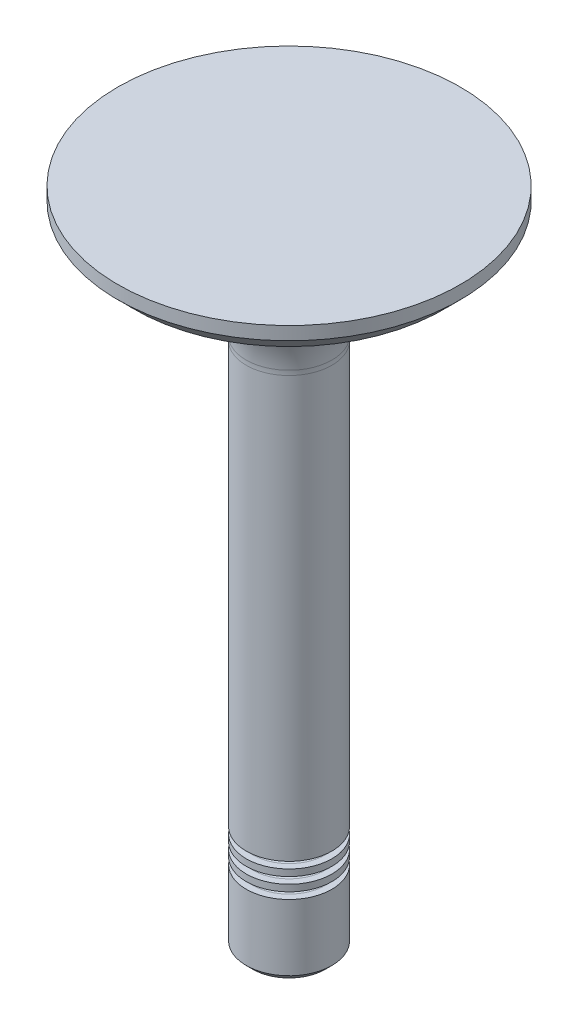
SolidWorks part; units mm, degrees
ref_plane "Front Plane" through (0, 0, 0) normal (0, 0, 1) x (1, 0, 0)
ref_plane "Top Plane" through (0, 0, 0) normal (0, 1, 0) x (1, 0, 0)
ref_plane "Right Plane" through (0, 0, 0) normal (1, 0, 0) x (0, 0, -1)
sketch "Sketch1" plane through (0, 0, 0) normal (0, 0, 1) x (1, 0, 0)
  line L0 (0, 224.083) -> (0, 124.083) construction
  line L1 (0, 224.083) -> (-25.92, 224.083)
  line L2 (-25.92, 224.083) -> (-25.92, 222.083)
  line L3 (-25.92, 222.083) -> (-23.328, 219.491)
  line L5 (-6.48, 204.053) -> (-6.48, 124.083)
  line L6 (-6.48, 124.083) -> (0, 124.083)
  line L7 (0, 224.083) -> (0, 124.083)
  arc A3 (-23.328, 219.491) -> (-6.48, 204.053) centre (-22.623, 203.348) cw
  dimension "D1" = 25.92
  dimension "D2" = 45
  dimension "D4" = 6.48
  dimension "D5" = 18.03
  dimension "D7" = 100
  dimension "D3" = 2.592
  dimension "D6" = 2
revolve "Revolve1" add sketch "Sketch1" angle 360 about L0
fillet "Fillet1" radius 10 1 edges at (-6.48, 204.053, 0)
chamfer "Chamfer1" distance 1 angle 45 1 edges at (-6.48, 124.083, 0)
sketch "Sketch5" plane through (0, 0, 0) normal (1, 0, 0) x (0, 0, -1)
  line L3 (-7.48, 138.083) -> (-5.48, 138.083)
  line L4 (0, 203.7831) -> (0, 125.083) construction
  line L5 (6.48, 203.7831) -> (-6.48, 203.7831) construction
  line L6 (6.48, 125.083) -> (-6.48, 125.083) construction
  line L7 (-7.48, 137.083) -> (-5.48, 137.083)
  line L8 (-7.48, 135.083) -> (-5.48, 135.083)
  line L9 (-7.48, 135.083) -> (-7.48, 136.083)
  line L10 (-7.48, 136.083) -> (-5.48, 136.083)
  line L12 (-7.48, 137.083) -> (-7.48, 138.083)
  line L13 (-7.48, 140.083) -> (-5.48, 140.083)
  line L14 (-7.48, 139.083) -> (-5.48, 139.083)
  line L15 (-7.48, 139.083) -> (-7.48, 140.083)
  arc A0 (-5.48, 135.083) -> (-5.48, 136.083) centre (-5.48, 135.583) ccw
  arc A1 (-5.48, 137.083) -> (-5.48, 138.083) centre (-5.48, 137.583) ccw
  arc A2 (-5.48, 139.083) -> (-5.48, 140.083) centre (-5.48, 139.583) ccw
  point P10 (-6.48, 135.583)
  dimension "D1" = 1
  dimension "D2" = 1
  dimension "D6" = 10
  dimension "D7" = 12
  dimension "D3" = 3
revolve "Cut-Revolve2" cut sketch "Sketch5" angle 360 about L4
equation "\"Valve Diameter\"= 51.84mm"
equation "\"Seat Angle Beta\"= 45deg"
equation "\"Seat Diameter\"= 46.656mm"
equation "\"Stem Diameter\"= 12.96mm"
equation "\"Max Lift\"= 18.03mm"
equation "\"Seat Width\"= 2.592mm"
equation "\"D1@Sketch1\"=\"Valve Diameter\"/2"
equation "\"D2@Sketch1\"=\"Seat Angle Beta\""
equation "\"D5@Sketch1\"=\"Max Lift\""
equation "\"Head Thickness\" = 2mm"
equation "\"Overall Length\"= 100mm"
equation "\"D7@Sketch1\"=\"Overall Length\""
equation "\"D3@Sketch1\"=\"Seat Width\""
equation "\"D6@Sketch1\"=\"Head Thickness\""
